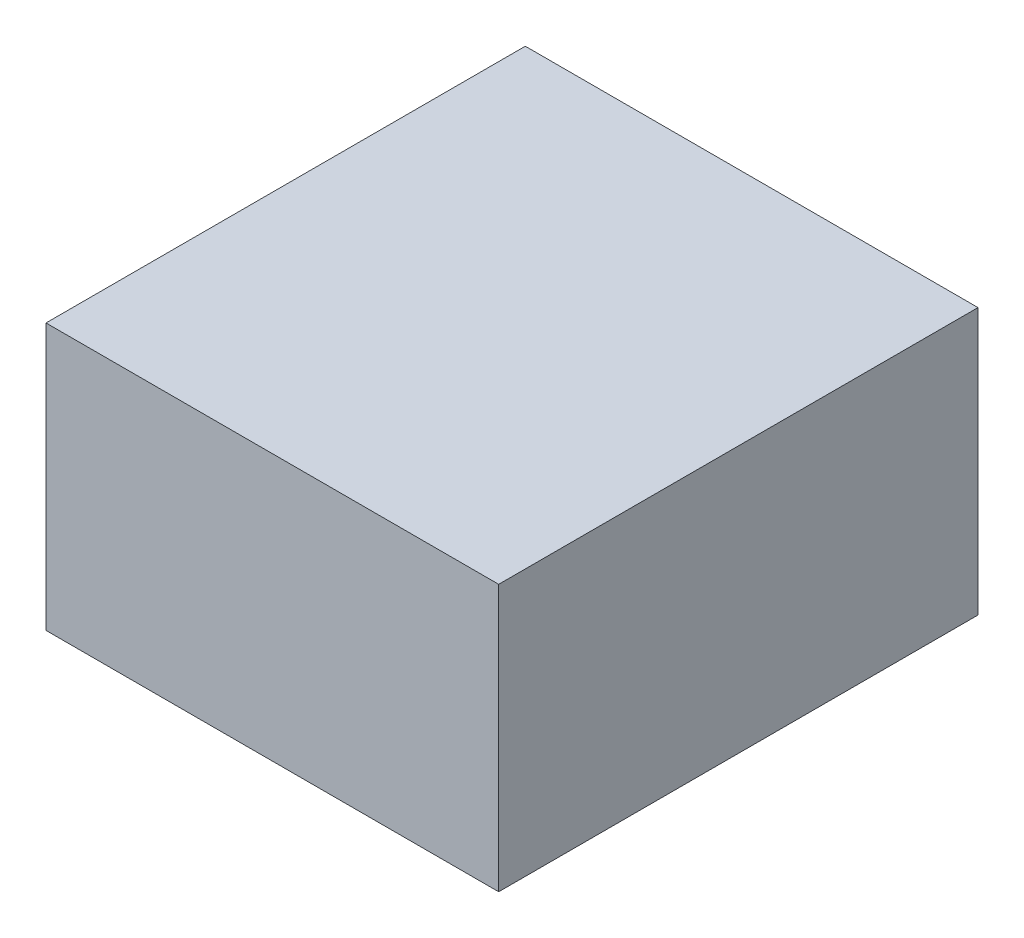
SolidWorks part; units mm, degrees
ref_plane "Front Plane" through (0, 0, 0) normal (0, 0, 1) x (1, 0, 0)
ref_plane "Top Plane" through (0, 0, 0) normal (0, 1, 0) x (1, 0, 0)
ref_plane "Right Plane" through (0, 0, 0) normal (1, 0, 0) x (0, 0, -1)
sketch "Sketch1" plane through (0, 0, 0) normal (0, 1, 0) x (1, 0, 0)
  line L1 (0, 0) -> (17, 0)
  line L2 (0, 0) -> (0, 18)
  line L3 (0, 18) -> (17, 18)
  line L4 (17, 0) -> (17, 18)
  dimension "D1" = 18
  dimension "D2" = 17
extrude "Boss-Extrude1" add sketch "Sketch1" along normal blind 10
